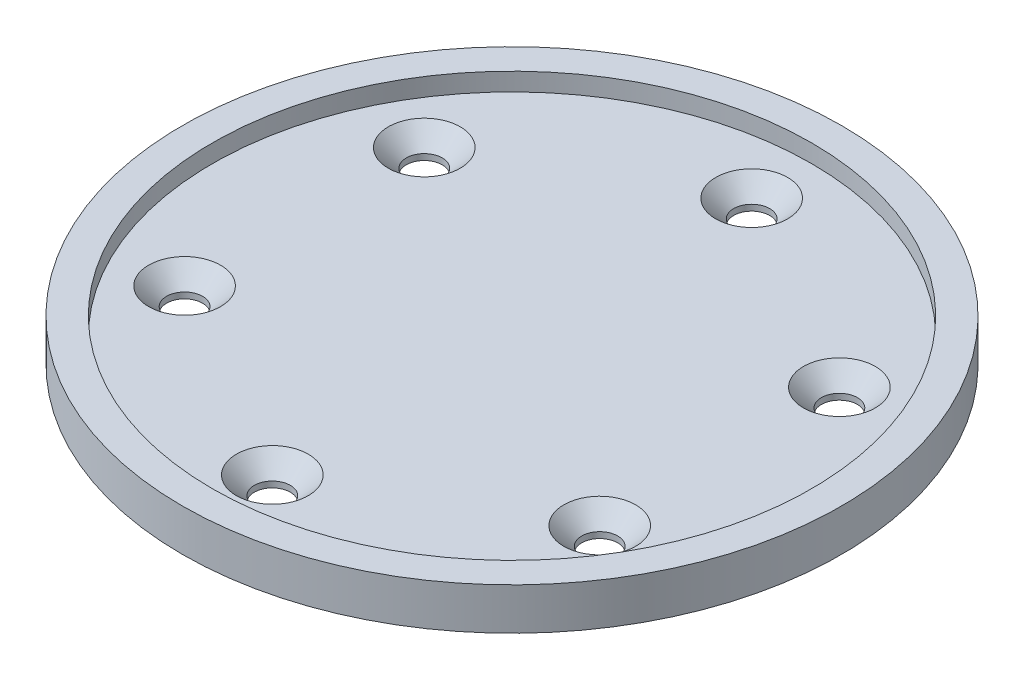
SolidWorks part; units mm, degrees
material "PBT General Purpose"
ref_plane "Front Plane" through (0, 0, 0) normal (0, 0, 1) x (1, 0, 0)
ref_plane "Top Plane" through (0, 0, 0) normal (0, 1, 0) x (1, 0, 0)
ref_plane "Right Plane" through (0, 0, 0) normal (1, 0, 0) x (0, 0, -1)
sketch "Sketch1" plane through (0, 0, 0) normal (0, 0, 1) x (1, 0, 0)
  line L0 (0, 0) -> (0, 21.4941) construction
  line L1 (50, 3.4786) -> (50, 6.4786)
  line L2 (50, 6.4786) -> (55, 6.4786)
  line L9 (50, 3.4786) -> (0, 3.4786)
  line L10 (0, -0.5214) -> (0, 3.4786)
  line L11 (0, -0.5214) -> (55, -0.5214)
  line L12 (55, -0.5214) -> (55, 6.4786)
  dimension "D1" = 0.5214
  dimension "D2" = 50
  dimension "D5" = 5
  dimension "D3" = 4
  dimension "D7" = 3
revolve "Revolve1" add sketch "Sketch1" angle 360 about L0
sketch "Sketch2" plane through (0, 3.4786, 0) normal (0, 1, 0) x (1, 0, 0)
  line L0 (0, 0) -> (0, 40) construction
  circle A0 centre (0, 40) radius 3
  circle A6 centre (34.641, 20) radius 3
  circle A7 centre (34.641, -20) radius 3
  circle A8 centre (0, -40) radius 3
  circle A9 centre (-34.641, -20) radius 3
  circle A10 centre (-34.641, 20) radius 3
  point P31 (0, 0)
  dimension "D1" = 6
  dimension "D2" = 40
  dimension "D3" = 6
extrude "Cut-Extrude1" cut sketch "Sketch2" against normal through all
chamfer "Chamfer1" distance 3 angle 45 6 edges at (0, 3.4786, -37) (34.641, 3.4786, -17) (34.641, 3.4786, 23) (0, 3.4786, 43) (-34.641, 3.4786, 23) (-34.641, 3.4786, -17)
sketch3d "3DSketch1"
  point P0 (-57, 29.4786, 57)
